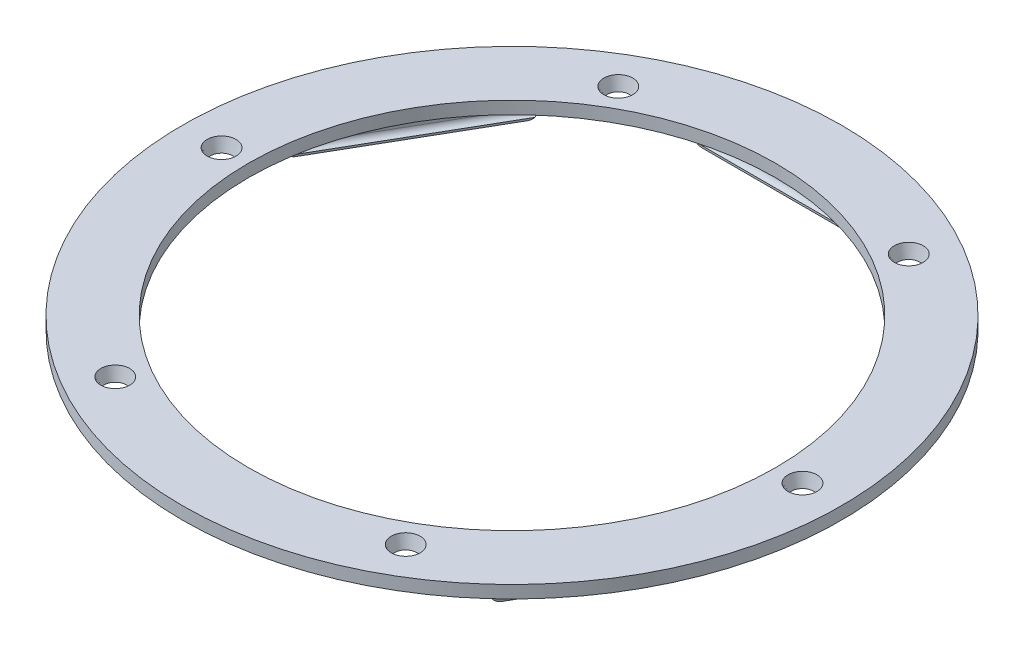
SolidWorks part; units mm, degrees
ref_plane "Front Plane" through (0, 0, 0) normal (0, 0, 1) x (1, 0, 0)
ref_plane "Top Plane" through (0, 0, 0) normal (0, 1, 0) x (1, 0, 0)
ref_plane "Right Plane" through (0, 0, 0) normal (1, 0, 0) x (0, 0, -1)
sketch "Sketch1" plane through (0, 0, 0) normal (0, 1, 0) x (1, 0, 0)
  line L0 (0, 0) -> (46.283, 0) construction
  line L1 (0, 0) -> (-23.135, 40.071) construction
  line L70 (0, 0) -> (0, 46.1) construction
  line L71 (50.5181, 0) -> (25.2591, 43.75) construction
  line L72 (25.2591, 43.75) -> (-25.2591, 43.75) construction
  line L73 (-25.2591, 43.75) -> (-50.5181, 0) construction
  line L74 (-50.5181, 0) -> (-25.2591, -43.75) construction
  line L75 (-25.2591, -43.75) -> (25.2591, -43.75) construction
  line L76 (25.2591, -43.75) -> (50.5181, 0) construction
  line L77 (-15, 46.1) -> (15, 46.1)
  line L78 (15, 46.1) -> (15, 43.75)
  line L79 (15, 43.75) -> (-15, 43.75)
  line L80 (-15, 43.75) -> (-15, 46.1)
  line L81 (30.3886, 34.8654) -> (32.4238, 36.0404)
  line L82 (32.4238, 36.0404) -> (47.4238, 10.0596)
  line L83 (47.4238, 10.0596) -> (45.3886, 8.8846)
  line L84 (53.2317, 0) -> (26.6158, 46.1) construction
  line L85 (26.6158, 46.1) -> (-26.6158, 46.1) construction
  line L86 (-26.6158, 46.1) -> (-53.2317, 0) construction
  line L87 (-53.2317, 0) -> (-26.6158, -46.1) construction
  line L88 (-26.6158, -46.1) -> (26.6158, -46.1) construction
  line L89 (26.6158, -46.1) -> (53.2317, 0) construction
  line L90 (45.3886, 8.8846) -> (30.3886, 34.8654)
  line L91 (45.3886, -8.8846) -> (47.4238, -10.0596)
  line L92 (47.4238, -10.0596) -> (32.4238, -36.0404)
  line L93 (32.4238, -36.0404) -> (30.3886, -34.8654)
  line L94 (30.3886, -34.8654) -> (45.3886, -8.8846)
  line L95 (15, -43.75) -> (15, -46.1)
  line L96 (15, -46.1) -> (-15, -46.1)
  line L97 (-15, -46.1) -> (-15, -43.75)
  line L98 (-15, -43.75) -> (15, -43.75)
  line L99 (-30.3886, -34.8654) -> (-32.4238, -36.0404)
  line L100 (-32.4238, -36.0404) -> (-47.4238, -10.0596)
  line L101 (-47.4238, -10.0596) -> (-45.3886, -8.8846)
  line L102 (-45.3886, -8.8846) -> (-30.3886, -34.8654)
  line L103 (-45.3886, 8.8846) -> (-47.4238, 10.0596)
  line L104 (-47.4238, 10.0596) -> (-32.4238, 36.0404)
  line L105 (-32.4238, 36.0404) -> (-30.3886, 34.8654)
  line L106 (-30.3886, 34.8654) -> (-45.3886, 8.8846)
  circle A0 centre (0, 0) radius 50
  circle A1 centre (0, 0) radius 46.27 construction
  circle A2 centre (-23.135, 40.071) radius 1
  circle A3 centre (0, 0) radius 45.14 construction
  circle A4 centre (23.135, 40.071) radius 1
  circle A5 centre (46.27, 0) radius 1
  circle A6 centre (23.135, -40.071) radius 1
  circle A7 centre (-23.135, -40.071) radius 1
  circle A8 centre (-46.27, 0) radius 1
  circle A9 centre (0, 0) radius 42
  circle A16 centre (0, 0) radius 43.75 construction
  circle A18 centre (0, 0) radius 46.1 construction
  point P10 (-22.57, 39.0924)
  point P36 (0, 0)
  point P47 (0, 0)
  point P59 (0, 46.1)
  point P84 (0, 0)
  point P98 (0, 0)
  dimension "D3" = 100
  dimension "D4" = 2
  dimension "D16" = 84
  dimension "D10" = 87.5
  dimension "D11" = 92.2
  dimension "D1" = 120
  dimension "D2" = 46.27
  dimension "D7" = 1.13
  dimension "D12" = 30
  dimension "D13" = 6
  dimension "D9" = 6
extrude "Boss-Extrude2" add sketch "Sketch1" along normal blind 1 and the other way blind 3.5 contours L98 L97 L96 L95
sketch "Sketch3" plane through (0, 0, 0) normal (0, 1, 0) x (1, 0, 0)
  line L0 (0, 0) -> (46.27, 0) construction
  line L1 (0, 0) -> (-23.135, 40.071) construction
  circle A0 centre (0, 0) radius 52.5
  circle A1 centre (0, 0) radius 42
  circle A2 centre (0, 0) radius 46.27 construction
  circle A3 centre (-23.135, 40.071) radius 1.5
  circle A4 centre (23.135, 40.071) radius 1.5
  circle A5 centre (46.27, 0) radius 1.5
  circle A6 centre (23.135, -40.071) radius 1.5
  circle A7 centre (-23.135, -40.071) radius 1.5
  circle A8 centre (-46.27, 0) radius 1.5
  point P21 (0, 0)
  dimension "D1" = 105
  dimension "D2" = 84
  dimension "D5" = 3
  dimension "D3" = 46.27
  dimension "D4" = 120
  dimension "D6" = 6
extrude "Boss-Extrude3" add sketch "Sketch3" along normal blind 2
chamfer "Chamfer1" distance 3 angle 15 6 edges at (23.135, 2, 41.571) (46.27, 2, 1.5) (23.135, 2, -38.571) (-23.135, 2, -38.571) (-46.27, 2, 1.5) (-23.135, 2, 41.571) first distance on face at (23.135, 2, 41.571) first distance on face at (46.27, 2, 1.5) first distance on face at (23.135, 2, -38.571) first distance on face at (-23.135, 2, -38.571) first distance on face at (-46.27, 2, 1.5) first distance on face at (-23.135, 2, 41.571)
fillet "Fillet1" radius 1.5 2 edges at (15, -3.5, 44.925) (-15, -3.5, 44.925)
hole_wizard "Ø1.0mm Dowel Slot1" positions "Sketch8" profile "Sketch7" size "Ø1.0" standard "ANSI Metric" slot yes end condition through all
sketch "Sketch8" plane through (-15, 0, 0) normal (-1, 0, 0) x (0, 0, 1)
  line L0 (43.4, -3.25) -> (43.4, -0.25) construction
  point P25 (43.4, -1.75)
  dimension "D1" = 3
sketch "Sketch7" plane through (-15, -1.75, 43.4) normal (0, 1, 0) x (0, 0, 1)
  line L0 (0, 0) -> (0, 67.5)
  line L1 (0, 67.5) -> (1, 67.5)
  line L2 (1, 67.5) -> (1, 0)
  line L5 (1, 0) -> (0, 0)
  line L11 (0, -6.35) -> (0, 107.95) construction
  dimension "Thru Hole Dia." = 2
  dimension "Thru Hole Depth" = 67.5
pattern_circular "CirPattern1" count 6 over 360 about axis through (0, 0, 0) along (0, 1, 0) of "Fillet1", "Boss-Extrude2", "Ø1.0mm Dowel Slot1"
